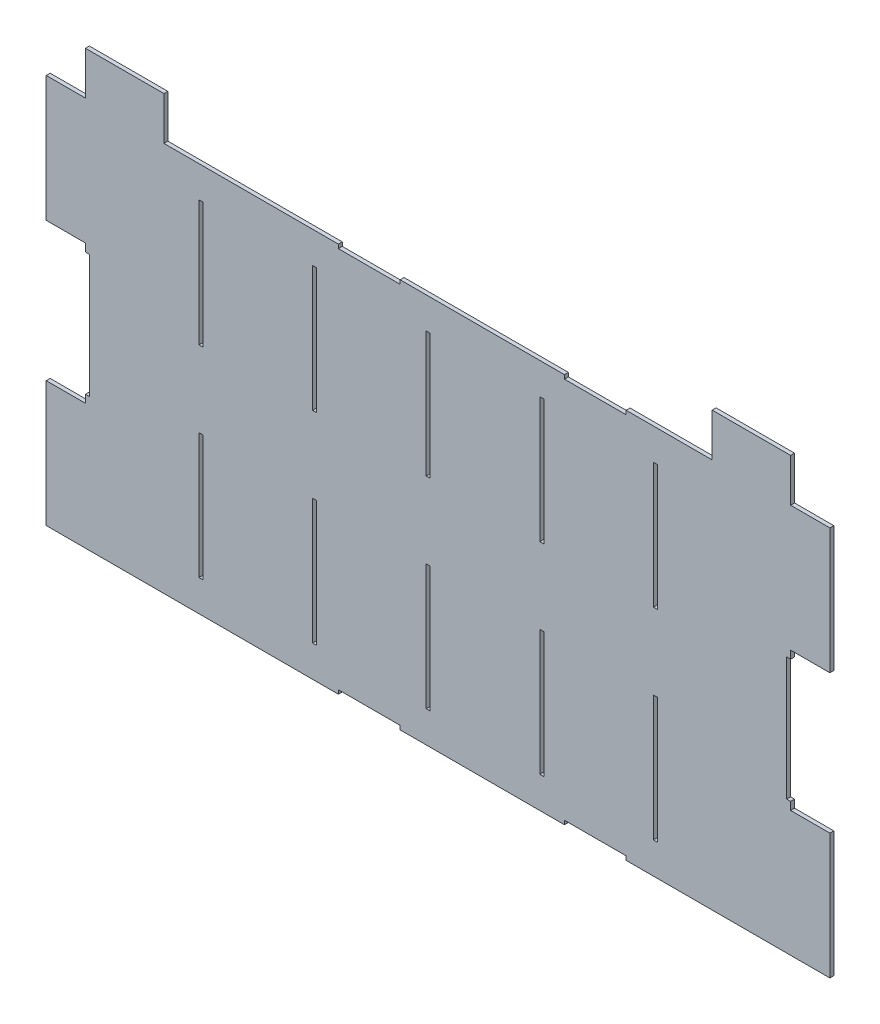
SolidWorks part; units mm, degrees
material "6061-T6 (SS)"
ref_plane "X-Y Datum" through (0, 0, 0) normal (0, 0, 1) x (1, 0, 0)
ref_plane "X-Z Datum" through (0, 0, 0) normal (0, 1, 0) x (1, 0, 0)
ref_plane "Y-Z Datum" through (0, 0, 0) normal (1, 0, 0) x (0, 0, -1)
sketch "Sketch1" plane through (0, 0, 0) normal (0, 0, 1) x (1, 0, 0)
  line L0 (-285.4305, 0) -> (285.4305, 0) construction
  line L1 (-285.4305, -157.7875) -> (285.4305, -157.7875)
  line L2 (-285.4305, -157.7875) -> (-285.4305, 157.7875)
  line L3 (-285.4305, 157.7875) -> (285.4305, 157.7875)
  line L4 (285.4305, -157.7875) -> (285.4305, 157.7875)
  line L5 (-285.4305, -157.7875) -> (285.4305, 157.7875) construction
  line L6 (-285.4305, 157.7875) -> (285.4305, -157.7875) construction
  line L7 (-282.2555, -154.615) -> (-282.2555, 154.615)
  line L8 (-280.6655, -153.025) -> (-195.0655, -153.025)
  line L9 (-280.6655, -153.025) -> (-280.6655, 153.025)
  line L10 (-280.6655, 153.025) -> (-195.0655, 153.025)
  line L11 (-195.0655, -153.025) -> (-195.0655, 153.025)
  line L12 (-280.6655, -153.025) -> (-195.0655, 153.025) construction
  line L13 (-280.6655, 153.025) -> (-195.0655, -153.025) construction
  line L14 (-282.2555, 154.615) -> (-193.4755, 154.615)
  line L15 (-193.4755, -154.615) -> (-193.4755, 154.615)
  line L16 (-282.2555, -154.615) -> (-193.4755, -154.615)
  line L17 (-190.3005, 154.615) -> (-101.5205, 154.615)
  line L18 (-188.7105, 153.025) -> (-103.1105, 153.025)
  line L19 (-190.3005, -154.615) -> (-190.3005, 154.615)
  line L20 (-188.7105, -153.025) -> (-188.7105, 153.025)
  line L21 (-101.5205, -154.615) -> (-101.5205, 154.615)
  line L22 (-103.1105, -153.025) -> (-103.1105, 153.025)
  line L23 (-188.7105, -153.025) -> (-103.1105, -153.025)
  line L24 (-190.3005, -154.615) -> (-101.5205, -154.615)
  line L25 (-188.7105, -153.025) -> (-103.1105, 153.025) construction
  line L26 (-188.7105, 153.025) -> (-103.1105, -153.025) construction
  line L27 (-98.3455, 154.615) -> (-9.5655, 154.615)
  line L28 (-96.7555, 153.025) -> (-11.1555, 153.025)
  line L29 (-98.3455, -154.615) -> (-98.3455, 154.615)
  line L30 (-96.7555, -153.025) -> (-96.7555, 153.025)
  line L31 (-9.5655, -154.615) -> (-9.5655, 154.615)
  line L32 (-11.1555, -153.025) -> (-11.1555, 153.025)
  line L33 (-96.7555, -153.025) -> (-11.1555, -153.025)
  line L34 (-98.3455, -154.615) -> (-9.5655, -154.615)
  line L35 (-96.7555, -153.025) -> (-11.1555, 153.025) construction
  line L36 (-96.7555, 153.025) -> (-11.1555, -153.025) construction
  line L37 (-6.3905, 154.615) -> (82.3895, 154.615)
  line L38 (-4.8005, 153.025) -> (80.7995, 153.025)
  line L39 (-6.3905, -154.615) -> (-6.3905, 154.615)
  line L40 (-4.8005, -153.025) -> (-4.8005, 153.025)
  line L41 (82.3895, -154.615) -> (82.3895, 154.615)
  line L42 (80.7995, -153.025) -> (80.7995, 153.025)
  line L43 (-4.8005, -153.025) -> (80.7995, -153.025)
  line L44 (-6.3905, -154.615) -> (82.3895, -154.615)
  line L45 (-4.8005, -153.025) -> (80.7995, 153.025) construction
  line L46 (-4.8005, 153.025) -> (80.7995, -153.025) construction
  line L47 (85.5645, 154.615) -> (174.3445, 154.615)
  line L48 (87.1545, 153.025) -> (172.7545, 153.025)
  line L49 (85.5645, -154.615) -> (85.5645, 154.615)
  line L50 (87.1545, -153.025) -> (87.1545, 153.025)
  line L51 (174.3445, -154.615) -> (174.3445, 154.615)
  line L52 (172.7545, -153.025) -> (172.7545, 153.025)
  line L53 (87.1545, -153.025) -> (172.7545, -153.025)
  line L54 (85.5645, -154.615) -> (174.3445, -154.615)
  line L55 (87.1545, -153.025) -> (172.7545, 153.025) construction
  line L56 (87.1545, 153.025) -> (172.7545, -153.025) construction
  point P0 (0, 0)
  point P8 (-237.8655, 0)
  dimension "D1" = 570.861
  dimension "D2" = 315.575
  dimension "D3" = 306.05
  dimension "D4" = 85.6
  dimension "D5" = 3.175
  dimension "D8" = 3.175
  dimension "D6" = 1.59
  dimension "D7" = 5
extrude "Boss-Extrude1" add sketch "Sketch1" along normal blind 3.175 contours L8 L11 L10 L9 | L20 L23 L22 L18 | L30 L33 L32 L28 | L50 L53 L52 L48 | L49 L54 L51 L47 L53 L50 L48 L52 | L1 L4 L3 L2 L54 L49 L47 L51 L44 L39 L37 L41 L34 L29 L27 L31 L24 L19 L17 L21 L16 L7 L14 L15 | L40 L43 L42 L38 | L7 L16 L15 L14 L11 L8 L9 L10 | L19 L24 L21 L17 L23 L20 L18 L22 | L29 L34 L31 L27 L33 L30 L28 L32 | L39 L44 L41 L37 L43 L40 L38 L42 region at (-284.7782, 0, 0) region at (-281.9338, 0, 0) region at (-237.8655, 0, 0) region at (-145.9105, 154.2933, 0) region at (-145.9105, 0, 0) region at (-53.9555, 154.2933, 0) region at (-53.9555, 0, 0) region at (37.9995, 154.2933, 0) region at (37.9995, 0, 0) region at (129.9545, 154.2933, 0) region at (129.9545, 0, 0)
sketch "Sketch2" plane through (0, 0, 3.175) normal (0, 0, 1) x (1, 0, 0)
  line L0 (-190.3005, -154.615) -> (-193.4755, -154.615) construction
  line L1 (-191.888, -154.615) -> (-191.888, 157.7875) construction
  line L2 (-285.4305, 157.7875) -> (285.4305, 157.7875) construction
  line L4 (-193.4755, -30.7875) -> (-190.3005, -30.7875)
  line L5 (-193.4755, -30.7875) -> (-193.4755, -132.3875)
  line L6 (-193.4755, -132.3875) -> (-190.3005, -132.3875)
  line L7 (-190.3005, -30.7875) -> (-190.3005, -132.3875)
  line L8 (-193.4755, -30.7875) -> (-190.3005, -132.3875) construction
  line L9 (-193.4755, -132.3875) -> (-190.3005, -30.7875) construction
  line L12 (-285.4305, -157.7875) -> (285.4305, -157.7875) construction
  point P8 (-191.888, -81.5875)
  dimension "D1" = 76.2
  dimension "D2" = 3.175
  dimension "D3" = 101.6
extrude "Cut-Extrude1" cut sketch "Sketch2" against normal blind 3.175
sketch "Sketch7" plane through (0, 0, 3.175) normal (0, 0, 1) x (1, 0, 0)
  line L0 (285.4305, -157.7875) -> (285.4305, 157.7875) construction
  line L1 (102.3049, -154.6125) -> (152.3049, -154.6125)
  line L2 (102.3049, -154.6125) -> (102.3049, -157.7875)
  line L3 (102.3049, -157.7875) -> (152.3049, -157.7875)
  line L4 (152.3049, -154.6125) -> (152.3049, -157.7875)
  line L5 (-80.6951, -154.6125) -> (-30.6951, -154.6125)
  line L6 (-80.6951, -154.6125) -> (-80.6951, -157.7875)
  line L7 (-80.6951, -157.7875) -> (-30.6951, -157.7875)
  line L8 (-30.6951, -154.6125) -> (-30.6951, -157.7875)
  dimension "D1" = 133
  dimension "D2" = 50
  dimension "D3" = 3.175
  dimension "D4" = 50
  dimension "D5" = 133.1256
extrude "Cut-Extrude5" cut sketch "Sketch7" against normal blind 3.175
mirror "Mirror3" about plane through (0, 0, 0) normal (0, 1, 0) of "Cut-Extrude1"
pattern_linear "LPattern2" count 5 spacing 91.96 along (1, 0, 0) of "Mirror3"
sketch "Sketch9" plane through (0, 0, 0) normal (0, 0, -1) x (-1, 0, 0)
  line L0 (-301.3055, -56.1875) -> (-301.3055, -157.7875) construction
  line L9 (-285.4305, 157.7875) -> (-221.9305, 157.7875)
  line L10 (-285.4305, 157.7875) -> (-285.4305, 192.7125)
  line L11 (-285.4305, 192.7125) -> (-221.9305, 192.7125)
  line L12 (-221.9305, 157.7875) -> (-221.9305, 192.7125)
  line L13 (-285.4305, 157.7875) -> (-317.1805, 157.7875)
  line L14 (-285.4305, 157.7875) -> (-285.4305, 56.1875)
  line L15 (-285.4305, 56.1875) -> (-317.1805, 56.1875)
  line L16 (-317.1805, 157.7875) -> (-317.1805, 56.1875)
  line L17 (-317.1805, 106.9875) -> (-285.4305, 106.9875) construction
  line L18 (-301.3055, 157.7875) -> (-301.3055, 113.3375)
  line L19 (-301.3055, 113.3375) -> (-301.3055, 56.1875) construction
  line L20 (-285.4305, -157.7875) -> (-317.1805, -157.7875)
  line L21 (-285.4305, -157.7875) -> (-285.4305, -88.7618)
  line L25 (-285.4305, -88.7618) -> (-285.4305, -56.1875)
  line L26 (-285.4305, -56.1875) -> (-317.1805, -56.1875)
  line L28 (-317.1805, -56.1875) -> (-317.1805, -157.7875)
  line L29 (-317.1805, -106.9875) -> (-285.4305, -106.9875) construction
  line L30 (-301.3055, -56.1875) -> (-301.3055, -106.9875) construction
  line L31 (-301.3055, -106.9875) -> (-301.3055, -157.7875) construction
  line L32 (-301.3055, -56.1875) -> (-301.3055, -106.9875) construction
  line L33 (-301.3055, -106.9875) -> (-301.3055, -157.7875) construction
  circle A0 centre (-301.3055, 135.5625) radius 3 construction
  circle A1 centre (-301.3055, 84.7625) radius 3 construction
  circle A2 centre (-301.3055, -81.5875) radius 3 construction
  circle A3 centre (-301.3055, -132.3875) radius 3 construction
  dimension "D1" = 6
  dimension "D2" = 6
  dimension "D3" = 63.5
  dimension "D4" = 34.925
  dimension "D5" = 101.6
  dimension "D6" = 31.75
  dimension "D7" = 31.75
  dimension "D8" = 101.6
extrude "Boss-Extrude3" add sketch "Sketch9" against normal blind 3.175 contours L13 L16 L15 L14 | L9 L12 L11 L10 | L26 L28 L20 L21 L25 A3 A2 region at (253.6805, 175.25, 0) region at (301.3055, 106.9875, 0) region at (301.3055, -106.9875, 0)
mirror "Mirror4" about plane through (0, 0, 0) normal (1, 0, 0) of "Boss-Extrude3"
mirror "Mirror5" about plane through (0, 0, 0) normal (0, 1, 0) of "Cut-Extrude5"
sketch "Sketch10" plane through (0, 0, 0) normal (0, 0, -1) x (-1, 0, 0)
  line L0 (-285.4305, 56.1875) -> (-285.4305, 49.8375)
  line L1 (-285.4305, -56.1875) -> (-285.4305, 56.1875) construction
  line L2 (-285.4305, -56.1875) -> (-317.1805, -56.1875) construction
  line L3 (-285.4305, 49.8375) -> (-282.2555, 49.8375)
  line L4 (-285.4305, 49.8375) -> (-285.4305, -49.8375)
  line L5 (-285.4305, -49.8375) -> (-282.2555, -49.8375)
  line L6 (-282.2555, 49.8375) -> (-282.2555, -49.8375)
  line L7 (-285.4305, 56.1875) -> (-317.1805, 56.1875) construction
  dimension "D1" = 6.35
  dimension "D2" = 3.175
  dimension "D3" = 6.35
extrude "Cut-Extrude6" cut sketch "Sketch10" against normal through all contours L6 L3 L4 L5 region at (283.843, 0, 0)
mirror "Mirror6" about plane through (0, 0, 0) normal (1, 0, 0) of "Cut-Extrude6"
